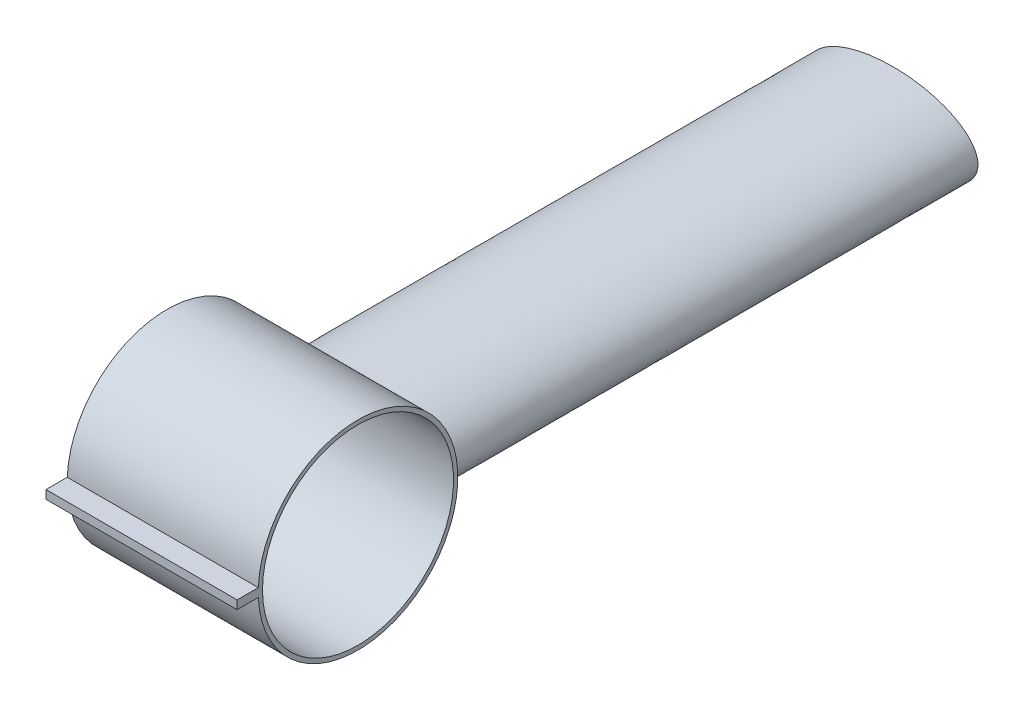
SolidWorks part; units mm, degrees
ref_plane "Front Plane" through (0, 0, 0) normal (0, 0, 1) x (1, 0, 0)
ref_plane "Top Plane" through (0, 0, 0) normal (0, 1, 0) x (1, 0, 0)
ref_plane "Right Plane" through (0, 0, 0) normal (1, 0, 0) x (0, 0, -1)
sketch "Clasp Sketch" plane through (0, 0, 0) normal (1, 0, 0) x (0, 0, -1)
  line L0 (-45, 0) -> (47, 0) construction
  line L4 (-56.9574, -2) -> (-56.9574, 2)
  line L5 (-56.9574, 2) -> (-46.9574, 2)
  line L6 (-56.9574, -2) -> (-46.9574, -2)
  circle A0 centre (0, 0) radius 45
  arc A1 (-46.9574, -2) -> (-46.9574, 2) centre (0, 0) ccw
  dimension "D1" = 45
  dimension "D2" = 2
  dimension "D3" = 4
  dimension "D4" = 10
extrude "Clasp Extrude" add sketch "Clasp Sketch" along normal blind 90
ref_plane "Shaft Plane" through (0, 0, -47) normal (0, 0, -1) x (-1, 0, 0)
sketch "Shaft Sketch" plane through (0, 0, -47) normal (0, 0, -1) x (-1, 0, 0)
  line L0 (-5, 0) -> (-85, 0) construction
  line L1 (-45, -20) -> (-45, 20) construction
  line L2 (0, 0) -> (-5, 0) construction
  line L3 (-85, 0) -> (-90, 0) construction
  line L4 (-90, 47) -> (-90, -47) construction
  line L5 (0, -47) -> (0, 47) construction
  ellipse E0 centre (-45, 0) end of major axis (-5, 0) minor radius 20
  dimension "D1" = 80
  dimension "D2" = 40
extrude "Shaft Extrude" add sketch "Shaft Sketch" against normal up to surface and the other way blind 250 up to face at (45, 0, -0.0213)
